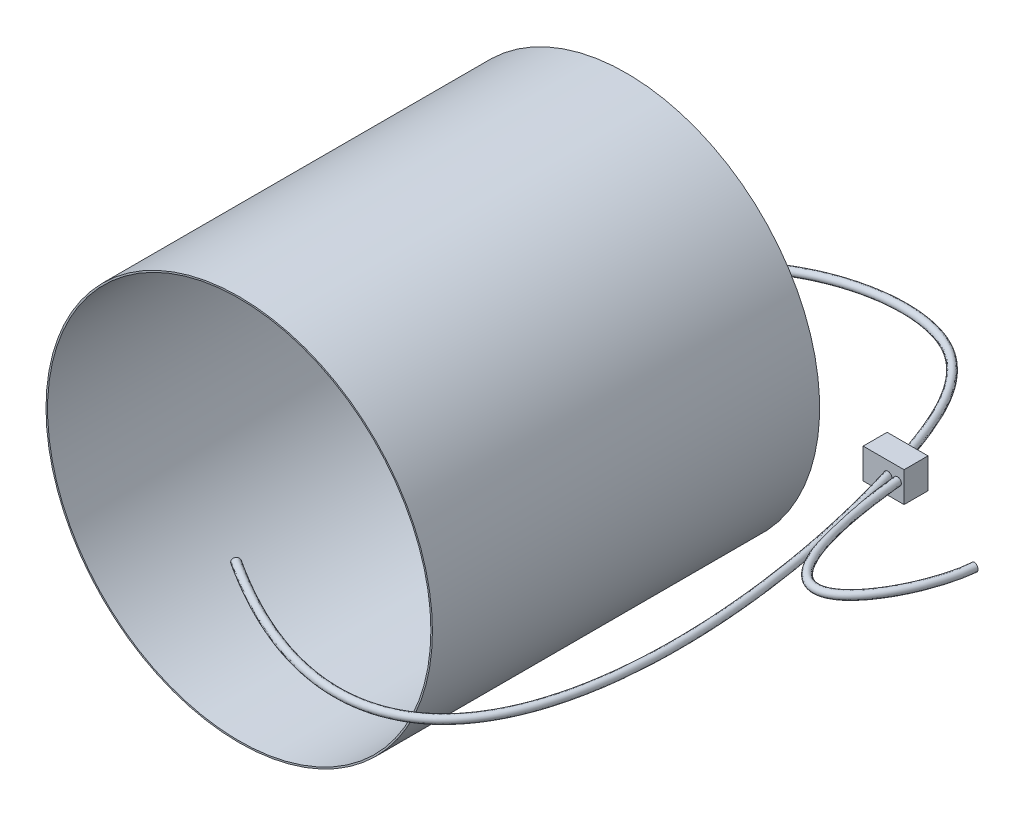
SolidWorks part; units mm, degrees
material "AISI 304"
ref_plane "Front Plane" through (0, 0, 0) normal (0, 0, 1) x (1, 0, 0)
ref_plane "Top Plane" through (0, 0, 0) normal (0, 1, 0) x (1, 0, 0)
ref_plane "Right Plane" through (0, 0, 0) normal (1, 0, 0) x (0, 0, -1)
sketch "Sketch1" plane through (0, 0, 0) normal (0, 0, 1) x (1, 0, 0)
  circle A0 centre (0, 0) radius 250
  circle A1 centre (0, 0) radius 248
  dimension "D1" = 500
  dimension "D2" = 2
extrude "Boss-Extrude1" add sketch "Sketch1" along normal blind 500
sketch "Sketch2" plane through (0, 0, 0) normal (0, 0, -1) x (-1, 0, 0)
  circle A0 centre (0, 0) radius 250
extrude "Boss-Extrude2" add sketch "Sketch2" along normal blind 1
sketch "Sketch3" plane through (0, 0, -1) normal (0, 0, -1) x (-1, 0, 0)
  circle A0 centre (0, 0) radius 5
  dimension "D1" = 10
sketch "Sketch5" plane through (0, 0, 0) normal (0, 1, 0) x (1, 0, 0)
  line L1 (250, 1) -> (-250, 1) construction
  spline S0 degree 3 poles (0, 1) (-12.3928, 126.3123) (261.9886, 239.6414) (470.6696, -232.3135) (472.1883, -825.9929) (45.2081, -549.2993) knots 0 0 0 0 0.237045 0.3654 1 1 1 1
sweep "Sweep2" add profiles "Sketch3" path "Sketch5"
sketch "Sketch6" plane through (0, 0, 0) normal (0, 0, 1) x (1, 0, 0)
  line L1 (338.3026, 17.1513) -> (391.2184, 17.1513)
  line L2 (338.3026, 17.1513) -> (338.3026, -21.998)
  line L3 (338.3026, -21.998) -> (391.2184, -21.998)
  line L4 (391.2184, 17.1513) -> (391.2184, -21.998)
  line L5 (338.3026, 17.1513) -> (391.2184, -21.998) construction
  line L6 (338.3026, -21.998) -> (391.2184, 17.1513) construction
  point P4 (364.7605, -2.4234)
extrude "Boss-Extrude3" add sketch "Sketch6" along normal blind 31 separate body
sketch "Sketch7" plane through (0, 0, 31) normal (0, 0, 1) x (1, 0, 0)
  circle A0 centre (382.7087, 0) radius 5
sketch "Sketch8" plane through (0, 0, 0) normal (0, 1, 0) x (1, 0, 0)
  line L0 (377.7087, -31) -> (387.7087, -31) construction
  spline S0 degree 3 poles (382.7087, -31) (414.3312, -339.5763) (522.7312, -157.9203) (528.967, -77.0978) knots 0 0 0 0 1 1 1 1
sweep "Sweep3" add profiles "Sketch7" path "Sketch8"
